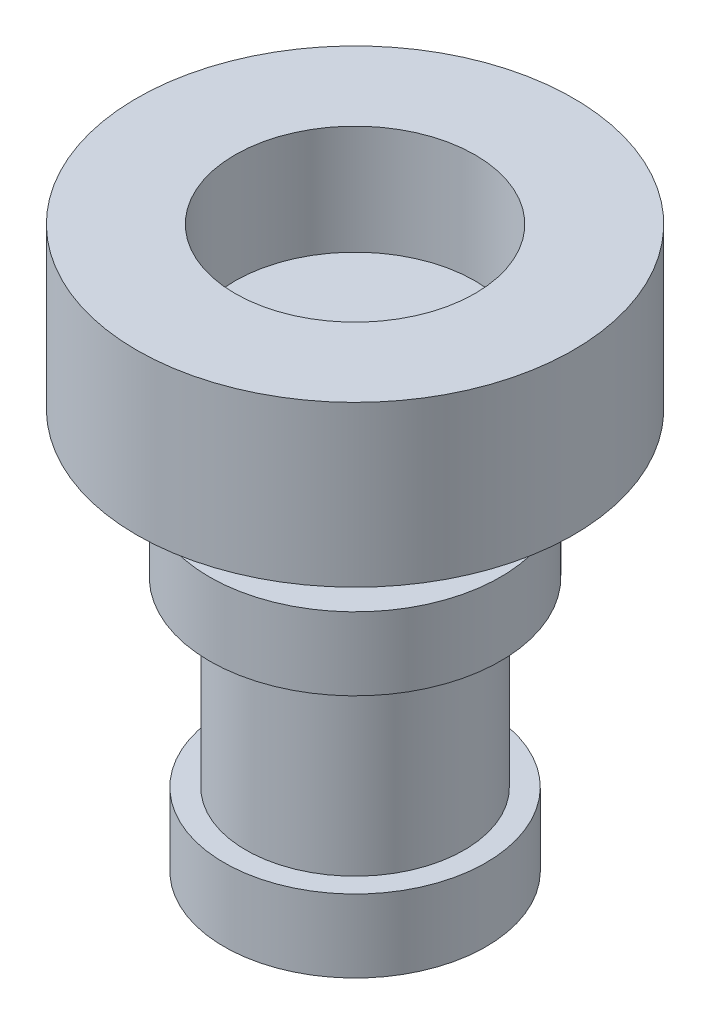
SolidWorks part; units mm, degrees
ref_plane "Front Plane" through (0, 0, 0) normal (0, 0, 1) x (1, 0, 0)
ref_plane "Top Plane" through (0, 0, 0) normal (0, 1, 0) x (1, 0, 0)
ref_plane "Right Plane" through (0, 0, 0) normal (1, 0, 0) x (0, 0, -1)
sketch "Sketch1" plane through (0, 0, 0) normal (0, 1, 0) x (1, 0, 0)
  circle A0 centre (-0.522, 0.5111) radius 1.6
  circle A1 centre (-0.522, 0.5111) radius 3
  dimension "D1" = 3.2
  dimension "D2" = 6
extrude "Boss-Extrude1" add sketch "Sketch1" along normal blind 2.2 contours A1
extrude "Boss-Extrude2" add sketch "Sketch1<3>" along normal blind 1 contours A0 region at (-0.522, 0, -0.5111)
sketch "Sketch1<3>" plane through (0, 0, 0) normal (0, 1, 0) x (1, 0, 0) same geometry as "Sketch1"
sketch "Sketch5" plane through (0, 0, 0) normal (0, -1, 0) x (1, 0, 0)
  circle A2 centre (-0.522, -0.5111) radius 1.5
  circle A3 centre (-0.522, -0.5111) radius 1.5
  dimension "D2" = 3
  dimension "D1" = 1.5
extrude "Boss-Extrude3" add sketch "Sketch5" along normal blind 1 contours A3
sketch "Sketch6" plane through (0, -1, 0) normal (0, -1, 0) x (1, 0, 0)
  circle A0 centre (-0.522, -0.5111) radius 2
  dimension "D1" = 4
extrude "Boss-Extrude4" add sketch "Sketch6" along normal blind 1
sketch "Sketch8" plane through (0, -2, 0) normal (0, -1, 0) x (-1, 0, 0)
  circle A0 centre (0.522, 0.5111) radius 1.5
  dimension "D1" = 3
extrude "Boss-Extrude5" add sketch "Sketch8" along normal blind 3.5 contours A0
sketch "Sketch10" plane through (0, -5.5, 0) normal (0, -1, 0) x (1, 0, 0)
  circle A0 centre (-0.522, -0.5111) radius 1.8
extrude "Boss-Extrude6" add sketch "Sketch10" against normal blind 1
sketch "Sketch11" plane through (0, 2.2, 0) normal (0, 1, 0) x (1, 0, 0)
  text T0 "VIII" font "Century Gothic" height in points 5
sketch "Sketch12" plane through (0, 2.2, 0) normal (0, 1, 0) x (1, 0, 0)
  circle A0 centre (-0.522, 0.5111) radius 1.65
extrude "Cut-Extrude1" cut sketch "Sketch12" against normal blind 1.5
